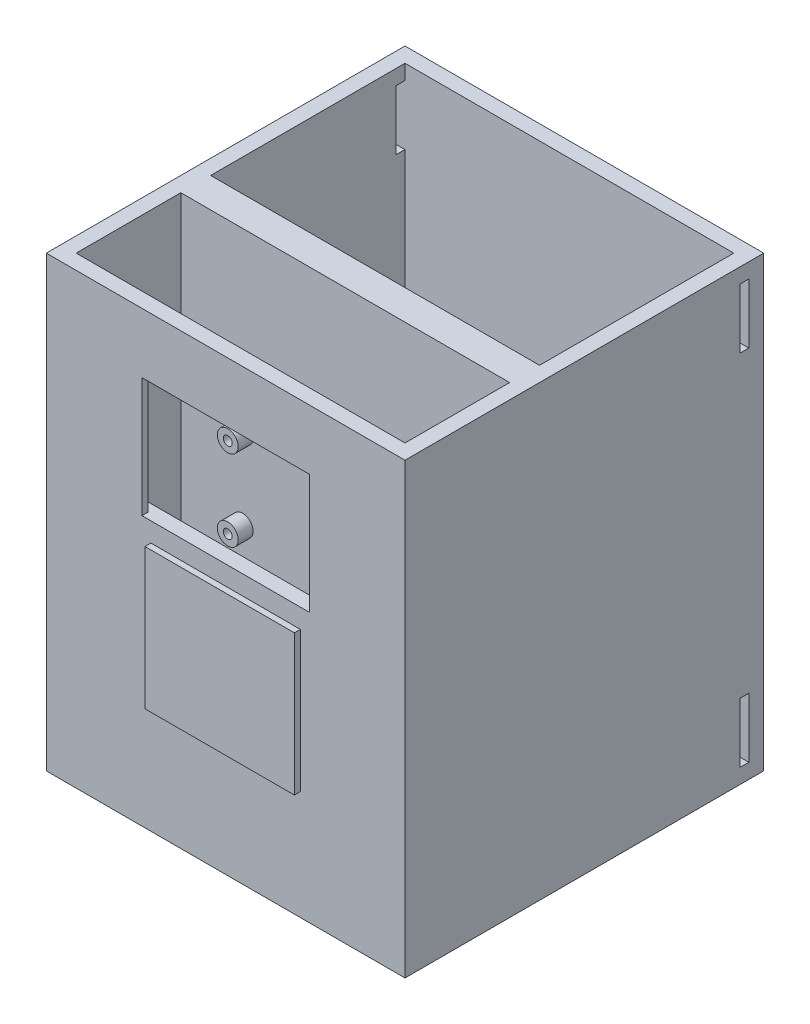
SolidWorks part; units mm, degrees
ref_plane "Front Plane" through (0, 0, 0) normal (0, 0, 1) x (1, 0, 0)
ref_plane "Top Plane" through (0, 0, 0) normal (0, 1, 0) x (1, 0, 0)
ref_plane "Right Plane" through (0, 0, 0) normal (1, 0, 0) x (0, 0, -1)
sketch "Sketch1" plane through (0, 0, 0) normal (0, 1, 0) x (1, 0, 0)
  line L1 (-60, -60) -> (60, -60)
  line L2 (-60, -60) -> (-60, 60)
  line L3 (-60, 60) -> (60, 60)
  line L4 (60, -60) -> (60, 60)
  line L5 (-60, -60) -> (60, 60) construction
  line L6 (-60, 60) -> (60, -60) construction
  point P0 (0, 0)
  dimension "D1" = 120
  dimension "D2" = 120
extrude "Boss-Extrude1" add sketch "Sketch1" along normal blind 150
shell "Shell1" thickness 5 removed face at (0, 150, 0)
sketch "Sketch3" plane through (0, 0, 0) normal (0, -1, 0) x (1, 0, 0)
  line L0 (60, 60) -> (60, -60) construction
  line L4 (-60, 60) -> (60, 60) construction
  circle A0 centre (0, 35) radius 2.5
  circle A1 centre (-5, 25) radius 1.5
  circle A2 centre (5, 25) radius 1.5
  dimension "D3" = 5
  dimension "D4" = 3
  dimension "D5" = 10
  dimension "D6" = 55
  dimension "D7" = 10
  dimension "D8" = 35
  dimension "D1" = 35
  dimension "D2" = 60
extrude "Cut-Extrude2" cut sketch "Sketch3" against normal up to next
sketch "Sketch4" plane through (0, 5, 0) normal (0, 1, 0) x (1, 0, 0)
  line L0 (-55, 55) -> (-55, -55) construction
  line L1 (-55, -20) -> (55, -20)
  line L2 (-55, -20) -> (-55, -10)
  line L3 (-55, -10) -> (55, -10)
  line L4 (55, -20) -> (55, -10)
  line L5 (55, -55) -> (55, 55) construction
  line L10 (-60, -60) -> (60, -60) construction
  dimension "D1" = 10
  dimension "D2" = 40
extrude "Boss-Extrude2" add sketch "Sketch4" along normal through all
sketch "Sketch5" plane through (0, 0, 60) normal (0, 0, 1) x (1, 0, 0)
  line L0 (60, 150) -> (60, 0) construction
  line L1 (-25, 36.5) -> (25, 36.5)
  line L2 (-25, 36.5) -> (-25, 83.5)
  line L3 (-25, 83.5) -> (25, 83.5)
  line L4 (25, 36.5) -> (25, 83.5)
  line L5 (-25, 36.5) -> (25, 83.5) construction
  line L6 (-25, 83.5) -> (25, 36.5) construction
  line L7 (-60, 150) -> (60, 150) construction
  point P0 (0, 60)
  dimension "D1" = 50
  dimension "D2" = 47
  dimension "D3" = 60
  dimension "D4" = 90
extrude "Boss-Extrude3" add sketch "Sketch5" along normal blind 2
sketch "Sketch8" plane through (0, 0, 60) normal (0, 0, 1) x (1, 0, 0)
  line L0 (-60, 150) -> (-60, 0) construction
  line L1 (-28, 89.9432) -> (28, 89.9432)
  line L2 (-28, 89.9432) -> (-28, 129.9432)
  line L3 (-28, 129.9432) -> (28, 129.9432)
  line L4 (28, 89.9432) -> (28, 129.9432)
  line L5 (-28, 89.9432) -> (28, 129.9432) construction
  line L6 (-28, 129.9432) -> (28, 89.9432) construction
  point P0 (0, 109.9432)
  dimension "D1" = 56
  dimension "D2" = 40
  dimension "D3" = 60
extrude "Cut-Extrude3" cut sketch "Sketch8" against normal up to next
sketch "Sketch9" plane through (0, 0, 55) normal (0, 0, -1) x (-1, 0, 0)
  line L17 (28, 89.9432) -> (-28, 89.9432) construction
  line L18 (-28, 129.9432) -> (-35.5, 129.9432)
  line L19 (-28, 129.9432) -> (-28, 89.9432)
  line L20 (-28, 89.9432) -> (-35.5, 89.9432)
  line L21 (-35.5, 129.9432) -> (-35.5, 89.9432)
  line L22 (-28, 89.9432) -> (-28, 129.9432) construction
  line L23 (0, 89.9432) -> (0, 129.9432) construction
  line L24 (-28, 129.9432) -> (28, 129.9432) construction
  line L25 (28, 89.9432) -> (35.5, 89.9432)
  line L26 (35.5, 129.9432) -> (35.5, 89.9432)
  line L27 (28, 129.9432) -> (35.5, 129.9432)
  line L28 (28, 129.9432) -> (28, 89.9432)
  dimension "D1" = 40
  dimension "D2" = 0
  dimension "D3" = 7.5
  dimension "D4" = 0
extrude "Cut-Extrude4" cut sketch "Sketch9" against normal offset from surface (3 mm away) 2 up to face at (0, 109.9432, 60)
sketch "Sketch10" plane through (0, 0, 62) normal (0, 0, 1) x (1, 0, 0)
  line L0 (-25, 36.5) -> (25, 36.5) construction
  line L1 (-22.5, 81) -> (22.5, 81)
  line L2 (-22.5, 81) -> (-22.5, 39)
  line L3 (-22.5, 39) -> (22.5, 39)
  line L4 (22.5, 81) -> (22.5, 39)
  line L5 (25, 36.5) -> (25, 83.5) construction
  dimension "D1" = 45
  dimension "D2" = 42
  dimension "D3" = 2.5
  dimension "D4" = 2.5
extrude "Cut-Extrude5" cut sketch "Sketch10" against normal up to next from offset 4 offset against normal yes
ref_plane "Plane1" through (0, 0, 0) normal (-1, 0, 0) x (0, 0, 1)
sketch "Sketch11" plane through (60, 0, 0) normal (1, 0, 0) x (0, 0, -1)
  line L0 (60, 150) -> (60, 0) construction
  line L1 (55, 5) -> (52, 5)
  line L2 (55, 5) -> (55, 25)
  line L3 (55, 25) -> (52, 25)
  line L4 (52, 5) -> (52, 25)
  line L5 (-60, 0) -> (60, 0) construction
  line L6 (-60, 75) -> (60, 75) construction
  line L7 (-60, 150) -> (-60, 0) construction
  line L8 (55, 125) -> (52, 125)
  line L9 (52, 145) -> (52, 125)
  line L10 (55, 145) -> (52, 145)
  line L11 (55, 145) -> (55, 125)
  dimension "D1" = 3
  dimension "D2" = 20
  dimension "D3" = 5
  dimension "D4" = 5
extrude "Cut-Extrude6" cut sketch "Sketch11" against normal up to next
mirror "Mirror1" about plane through (0, 0, 0) normal (-1, 0, 0) of "Cut-Extrude6"
sketch "Sketch12" plane through (0, 0, 20) normal (0, 0, 1) x (1, 0, 0)
  line L0 (0, 5) -> (0, 150) construction
  line L1 (-55, 5) -> (55, 5) construction
  line L2 (-55, 150) -> (55, 150) construction
  line L3 (-55, 77.5) -> (55, 77.5) construction
  line L4 (-55, 150) -> (-55, 5) construction
  line L5 (55, 150) -> (55, 5) construction
  circle A0 centre (-34.29, 91) radius 3.5
  circle A1 centre (34.29, 91) radius 3.5
  circle A2 centre (34.29, 64) radius 3.5
  circle A3 centre (-34.29, 64) radius 3.5
  circle A4 centre (-34.29, 91) radius 1.5
  circle A5 centre (34.29, 91) radius 1.5
  circle A6 centre (34.29, 64) radius 1.5
  circle A7 centre (-34.29, 64) radius 1.5
  dimension "D1" = 7
  dimension "D2" = 34.29
  dimension "D3" = 13.5
  dimension "D4" = 3
extrude "Boss-Extrude4" add sketch "Sketch12" along normal blind 5
